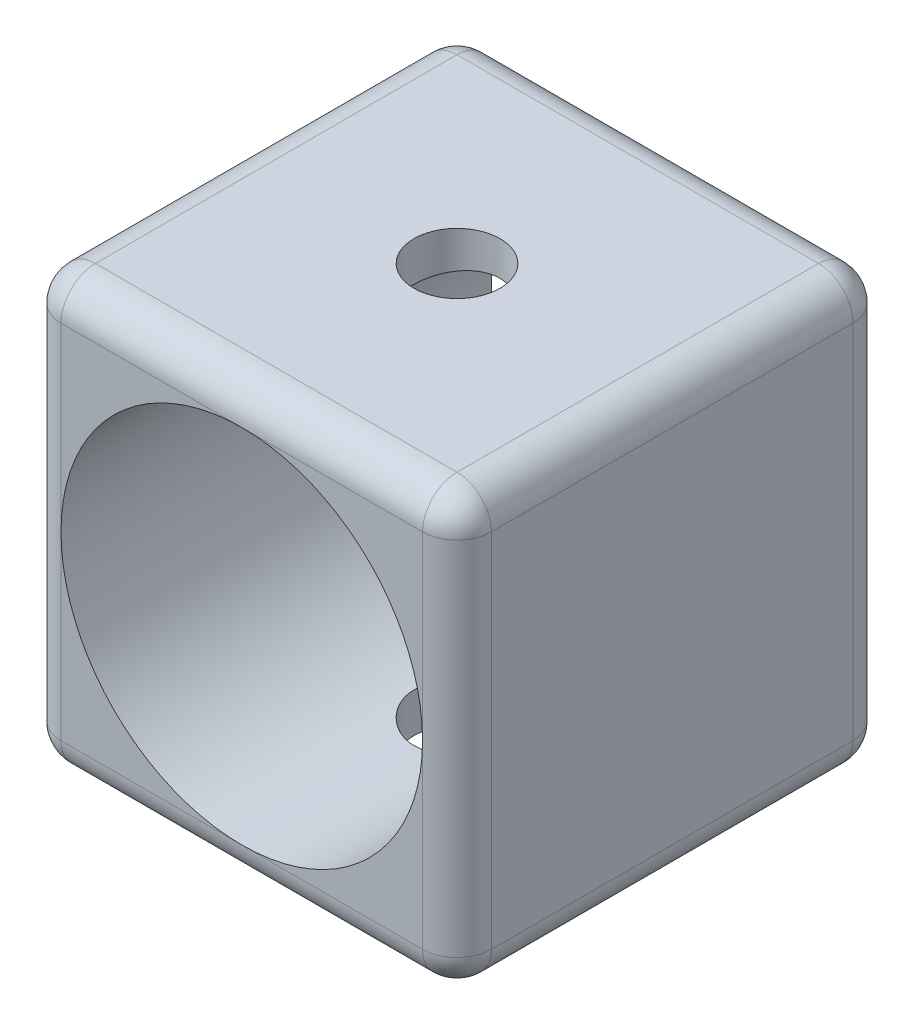
SolidWorks part; units mm, degrees
ref_plane "Front Plane" through (0, 0, 0) normal (0, 0, 1) x (1, 0, 0)
ref_plane "Top Plane" through (0, 0, 0) normal (0, 1, 0) x (1, 0, 0)
ref_plane "Right Plane" through (0, 0, 0) normal (1, 0, 0) x (0, 0, -1)
sketch "Sketch1" plane through (0, 0, 0) normal (0, 1, 0) x (1, 0, 0)
  line L1 (12.5, -12.5) -> (-12.5, -12.5)
  line L2 (12.5, -12.5) -> (12.5, 12.5)
  line L3 (12.5, 12.5) -> (-12.5, 12.5)
  line L4 (-12.5, -12.5) -> (-12.5, 12.5)
  line L5 (12.5, -12.5) -> (-12.5, 12.5) construction
  line L6 (12.5, 12.5) -> (-12.5, -12.5) construction
  point P0 (0, 0)
  dimension "D1" = 25
  dimension "D2" = 25
extrude "Boss-Extrude1" add sketch "Sketch1" along normal blind 25
sketch "Sketch2" plane through (0, 0, 12.5) normal (0, 0, 1) x (1, 0, 0)
  circle A0 centre (0, 12.5) radius 10.5
  dimension "D1" = 21
extrude "Cut-Extrude1" cut sketch "Sketch2" against normal up to surface (25 mm away) up to face at (0, 12.5, -12.5)
sketch "Sketch3" plane through (0, 25, 0) normal (0, 1, 0) x (1, 0, 0)
  circle A0 centre (0, 0) radius 2.5
  dimension "D1" = 5
extrude "Cut-Extrude2" cut sketch "Sketch3" against normal up to surface (25 mm away) up to face at (0, 0, 0)
fillet "Fillet1" radius 2 12 edges at (-12.5, 12.5, -12.5) (0, 0, -12.5) (-12.5, 0, 0) (12.5, 12.5, -12.5) (12.5, 0, 0) (-12.5, 12.5, 12.5) (12.5, 12.5, 12.5) (0, 0, 12.5) (0, 25, -12.5) (12.5, 25, 0) (0, 25, 12.5) (-12.5, 25, 0)
